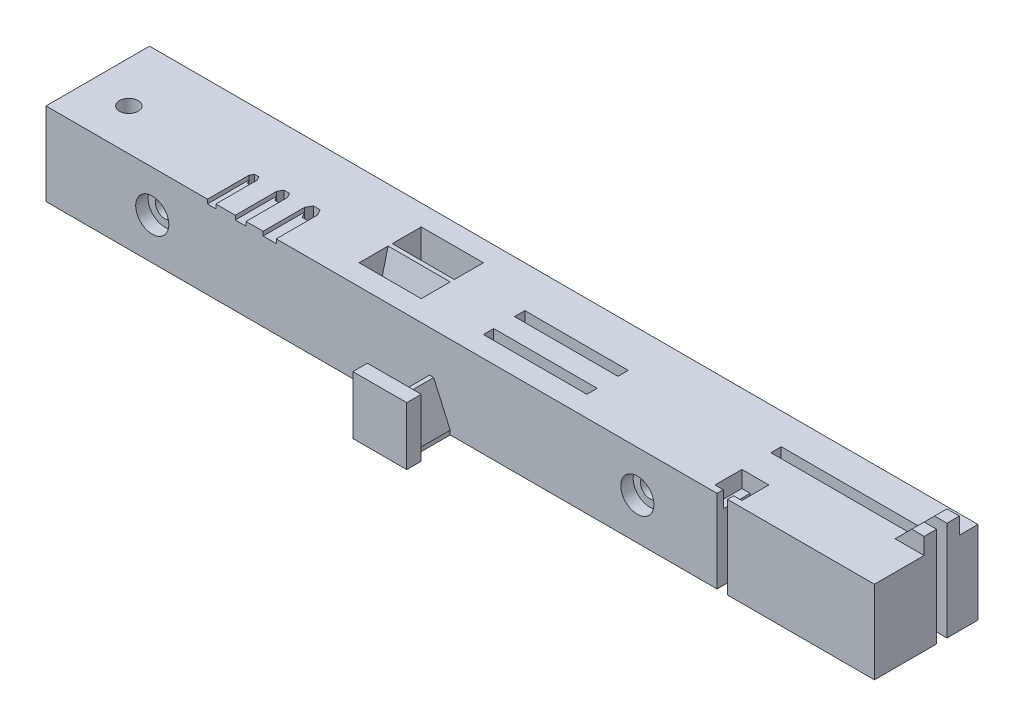
SolidWorks part; units mm, degrees
ref_plane "Piano frontale" through (0, 0, 0) normal (0, 0, 1) x (1, 0, 0)
ref_plane "Piano superiore" through (0, 0, 0) normal (0, 1, 0) x (1, 0, 0)
ref_plane "Piano destro" through (0, 0, 0) normal (1, 0, 0) x (0, 0, -1)
sketch "Schizzo1" plane through (0, 0, 0) normal (0, 0, 1) x (1, 0, 0)
  line L1 (-63.299, 14.3184) -> (136.701, 14.3184)
  line L2 (-63.299, 14.3184) -> (-63.299, -5.6816)
  line L3 (-63.299, -5.6816) -> (136.701, -5.6816)
  line L4 (136.701, 14.3184) -> (136.701, -5.6816)
  dimension "D1" = 20
  dimension "D2" = 200
extrude "Estrusione-Estrusione1" add sketch "Schizzo1" along normal blind 25
sketch "Schizzo2" plane through (0, 14.3184, 0) normal (0, 1, 0) x (1, 0, 0)
  line L0 (136.701, 0) -> (-63.299, 0) construction
  line L2 (-63.299, -25) -> (-63.299, 0) construction
  line L3 (-23.8041, -15.875) -> (-22.7938, -15.875)
  line L4 (-22.7938, -15.875) -> (-22.2886, -15)
  line L5 (-22.2886, -15) -> (-22.7938, -14.125)
  line L6 (-22.7938, -14.125) -> (-23.8041, -14.125)
  line L7 (-23.8041, -14.125) -> (-24.3093, -15)
  line L8 (-24.3093, -15) -> (-23.8041, -15.875)
  line L9 (-14.9999, -15) -> (-15.6494, -13.875)
  line L10 (-15.6494, -13.875) -> (-16.9485, -13.875)
  line L11 (-16.9485, -13.875) -> (-17.598, -15)
  line L12 (-17.598, -15) -> (-16.9485, -16.125)
  line L13 (-16.9485, -16.125) -> (-15.6494, -16.125)
  line L14 (-15.6494, -16.125) -> (-14.9999, -15)
  line L15 (-8.5051, -16.375) -> (-7.7113, -15)
  line L16 (-7.7113, -15) -> (-8.5051, -13.625)
  line L17 (-8.5051, -13.625) -> (-10.0928, -13.625)
  line L18 (-10.0928, -13.625) -> (-10.8867, -15)
  line L19 (-10.8867, -15) -> (-10.0928, -16.375)
  line L20 (-10.0928, -16.375) -> (-8.5051, -16.375)
  circle A0 centre (-53.299, -15) radius 2.25
  circle A1 centre (-23.299, -15) radius 0.875 construction
  circle A2 centre (-16.299, -15) radius 1.125 construction
  circle A3 centre (-9.299, -15) radius 1.375 construction
  dimension "D2" = 4.5
  dimension "D4" = 1.75
  dimension "D5" = 2.25
  dimension "D6" = 2.75
  dimension "D1" = 15
  dimension "D3" = 10
  dimension "D7" = 30
  dimension "D8" = 7
  dimension "D9" = 7
  dimension "D10" = 15
  dimension "D11" = 15
  dimension "D12" = 15
extrude "Taglio-Estrusione1" cut sketch "Schizzo2" against normal through all
sketch "Schizzo4" plane through (0, 14.3184, 0) normal (0, 1, 0) x (1, 0, 0)
  line L0 (136.701, -25) -> (-63.299, -25) construction
  line L1 (-24.3093, -15) -> (-22.2886, -15)
  line L2 (-24.3093, -15) -> (-24.3093, -25)
  line L3 (-24.3093, -25) -> (-22.2886, -25)
  line L4 (-22.2886, -15) -> (-22.2886, -25)
  line L5 (-17.598, -15) -> (-14.9999, -15)
  line L6 (-17.598, -15) -> (-17.598, -25)
  line L7 (-17.598, -25) -> (-14.9999, -25)
  line L8 (-14.9999, -15) -> (-14.9999, -25)
  line L10 (-10.8867, -15) -> (-7.7113, -15)
  line L11 (-10.8867, -15) -> (-10.8867, -25)
  line L12 (-10.8867, -25) -> (-7.7113, -25)
  line L13 (-7.7113, -15) -> (-7.7113, -25)
extrude "Taglio-Estrusione2" cut sketch "Schizzo4" against normal blind 1
sketch "Schizzo7" plane through (0, 14.3184, 0) normal (0, 1, 0) x (1, 0, 0)
  line L0 (136.701, -25) -> (-7.7113, -25) construction
  line L1 (7.2887, -14.5) -> (22.2887, -14.5)
  line L2 (7.2887, -14.5) -> (7.2887, -20)
  line L3 (7.2887, -20) -> (22.2887, -20)
  line L4 (22.2887, -14.5) -> (22.2887, -20)
  line L5 (7.2887, -5) -> (22.2887, -5)
  line L6 (7.2887, -5) -> (7.2887, -10.5)
  line L7 (7.2887, -10.5) -> (22.2887, -10.5)
  line L8 (22.2887, -5) -> (22.2887, -10.5)
  dimension "D1" = 15
  dimension "D2" = 15
  dimension "D3" = 15
  dimension "D4" = 4
  dimension "D5" = 5.5
  dimension "D6" = 5
  dimension "D7" = 15
extrude "Taglio-Estrusione3" cut sketch "Schizzo7" against normal through all
chamfer "Smusso1" distance 1.5 distance2 6 2 edges at (14.7887, 14.3184, 14.5) (14.7887, 14.3184, 10.5) first distance on face at (14.7887, 14.3184, 7.75)
sketch "Schizzo8" plane through (0, 14.3184, 0) normal (0, 1, 0) x (1, 0, 0)
  line L0 (7.2887, -20) -> (22.2887, -20) construction
  line L1 (37.2887, -17.5) -> (62.2887, -17.5)
  line L2 (37.2887, -17.5) -> (37.2887, -20)
  line L3 (37.2887, -20) -> (62.2887, -20)
  line L4 (62.2887, -17.5) -> (62.2887, -20)
  line L5 (37.2887, -10) -> (62.2887, -10)
  line L6 (37.2887, -10) -> (37.2887, -12.5)
  line L7 (37.2887, -12.5) -> (62.2887, -12.5)
  line L8 (62.2887, -10) -> (62.2887, -12.5)
  line L9 (22.2887, -12) -> (22.2887, -5) construction
  point P10 (22.2887, -8.5)
  dimension "D1" = 25
  dimension "D2" = 25
  dimension "D3" = 2.5
  dimension "D4" = 2.5
  dimension "D5" = 5
  dimension "D6" = 15
extrude "Taglio-Estrusione4" cut sketch "Schizzo8" against normal blind 13
sketch "Schizzo9" plane through (0, 14.3184, 0) normal (0, 1, 0) x (1, 0, 0)
  line L0 (136.701, -25) -> (136.701, 0) construction
  line L1 (96.701, -7.5) -> (136.701, -7.5)
  line L2 (96.701, -7.5) -> (96.701, -10)
  line L3 (96.701, -10) -> (136.701, -10)
  line L4 (136.701, -7.5) -> (136.701, -10)
  line L5 (136.701, 0) -> (-63.299, 0) construction
  dimension "D1" = 40
  dimension "D2" = 2.5
  dimension "D3" = 7.5
extrude "Taglio-Estrusione5" cut sketch "Schizzo9" against normal through all
sketch "Schizzo10" plane through (0, 14.3184, 0) normal (0, 1, 0) x (1, 0, 0)
  line L1 (136.701, -7.5) -> (129.701, -7.5)
  line L2 (136.701, -7.5) -> (136.701, -4.5)
  line L3 (136.701, -4.5) -> (129.701, -4.5)
  line L4 (129.701, -7.5) -> (129.701, -4.5)
  line L5 (136.701, -10) -> (129.701, -10)
  line L6 (136.701, -10) -> (136.701, -13)
  line L7 (136.701, -13) -> (129.701, -13)
  line L8 (129.701, -10) -> (129.701, -13)
  dimension "D1" = 7
  dimension "D2" = 7
  dimension "D3" = 3
  dimension "D4" = 3
extrude "Estrusione-Estrusione5" add sketch "Schizzo10" along normal blind 4
chamfer "Smusso2" distance 4 angle 45 2 edges at (129.701, 18.3184, 11.5) (129.701, 18.3184, 6)
sketch "Schizzo11" plane through (0, 14.3184, 0) normal (0, 1, 0) x (1, 0, 0)
  line L0 (136.701, -25) -> (-7.7113, -25) construction
  line L1 (98.701, -25) -> (101.201, -25)
  line L2 (98.701, -25) -> (98.701, -17)
  line L3 (98.701, -17) -> (101.201, -17)
  line L4 (101.201, -25) -> (101.201, -17)
  line L5 (96.701, -7.5) -> (96.701, -10) construction
  dimension "D1" = 2.5
  dimension "D2" = 8
  dimension "D3" = 2
extrude "Taglio-Estrusione6" cut sketch "Schizzo11" against normal through all
sketch "Schizzo12" plane through (0, 14.3184, 0) normal (0, 1, 0) x (1, 0, 0)
  line L0 (101.201, -17) -> (98.701, -17) construction
  line L1 (96.701, -17) -> (103.201, -17)
  line L2 (96.701, -17) -> (96.701, -23.5)
  line L3 (96.701, -23.5) -> (103.201, -23.5)
  line L4 (103.201, -17) -> (103.201, -23.5)
  line L7 (96.701, -7.5) -> (96.701, -10) construction
  dimension "D1" = 6.5
  dimension "D2" = 6.5
extrude "Taglio-Estrusione7" cut sketch "Schizzo12" against normal blind 4
sketch "Schizzo13" plane through (0, 0, 25) normal (0, 0, 1) x (1, 0, 0)
  line L0 (-63.299, -5.6816) -> (98.701, -5.6816) construction
  line L1 (25.2887, 4.3184) -> (34.2887, 4.3184)
  line L2 (25.2887, 4.3184) -> (25.2887, -5.6816)
  line L3 (25.2887, -5.6816) -> (34.2887, -5.6816)
  line L4 (34.2887, 4.3184) -> (34.2887, -5.6816)
  dimension "D1" = 10
  dimension "D2" = 3
  dimension "D3" = 9
extrude "Estrusione-Estrusione9" add sketch "Schizzo13" along normal blind 9 contours L2 L3 L4 L1
sketch "Schizzo14" plane through (0, 0, 34) normal (0, 0, 1) x (1, 0, 0)
  line L0 (25.2887, -5.6816) -> (34.2887, -5.6816) construction
  line L1 (23.2887, 8.3184) -> (36.2887, 8.3184)
  line L2 (23.2887, 8.3184) -> (23.2887, -5.6816)
  line L3 (23.2887, -5.6816) -> (36.2887, -5.6816)
  line L4 (36.2887, 8.3184) -> (36.2887, -5.6816)
  line L5 (25.2887, 4.3184) -> (25.2887, -5.6816) construction
  dimension "D1" = 13
  dimension "D2" = 14
  dimension "D3" = 2
extrude "Estrusione-Estrusione10" add sketch "Schizzo14" along normal blind 3.5
chamfer "Smusso3" distance 9 distance2 4 1 edges at (34.2887, 4.3184, 29.5) first distance on face at (34.2887, 0.5684, 30.625)
chamfer "Smusso4" distance 4 distance2 9 1 edges at (25.2887, 4.3184, 29.5) first distance on face at (27.7887, 4.3184, 29.5)
sketch "Schizzo16" plane through (0, 0, 25) normal (0, 0, 1) x (1, 0, 0)
  line L2 (-24.3093, 14.3184) -> (-63.299, 14.3184) construction
  line L3 (98.701, 14.3184) -> (-7.7113, 14.3184) construction
  circle A0 centre (-37.649, 4.3184) radius 2.25
  circle A1 centre (79.451, 4.3184) radius 2.25
  dimension "D3" = 4.5
  dimension "D4" = 4.5
  dimension "D1" = 17.25
  dimension "D2" = 13.4
  dimension "D5" = 10
  dimension "D6" = 10
extrude "Taglio-Estrusione8" cut sketch "Schizzo16" against normal through all
sketch "Schizzo17" plane through (0, 0, 25) normal (0, 0, 1) x (1, 0, 0)
  circle A0 centre (-37.649, 4.3184) radius 4
  circle A1 centre (79.451, 4.3184) radius 4
  dimension "D1" = 8
  dimension "D2" = 8
extrude "Taglio-Estrusione9" cut sketch "Schizzo17" against normal blind 3
